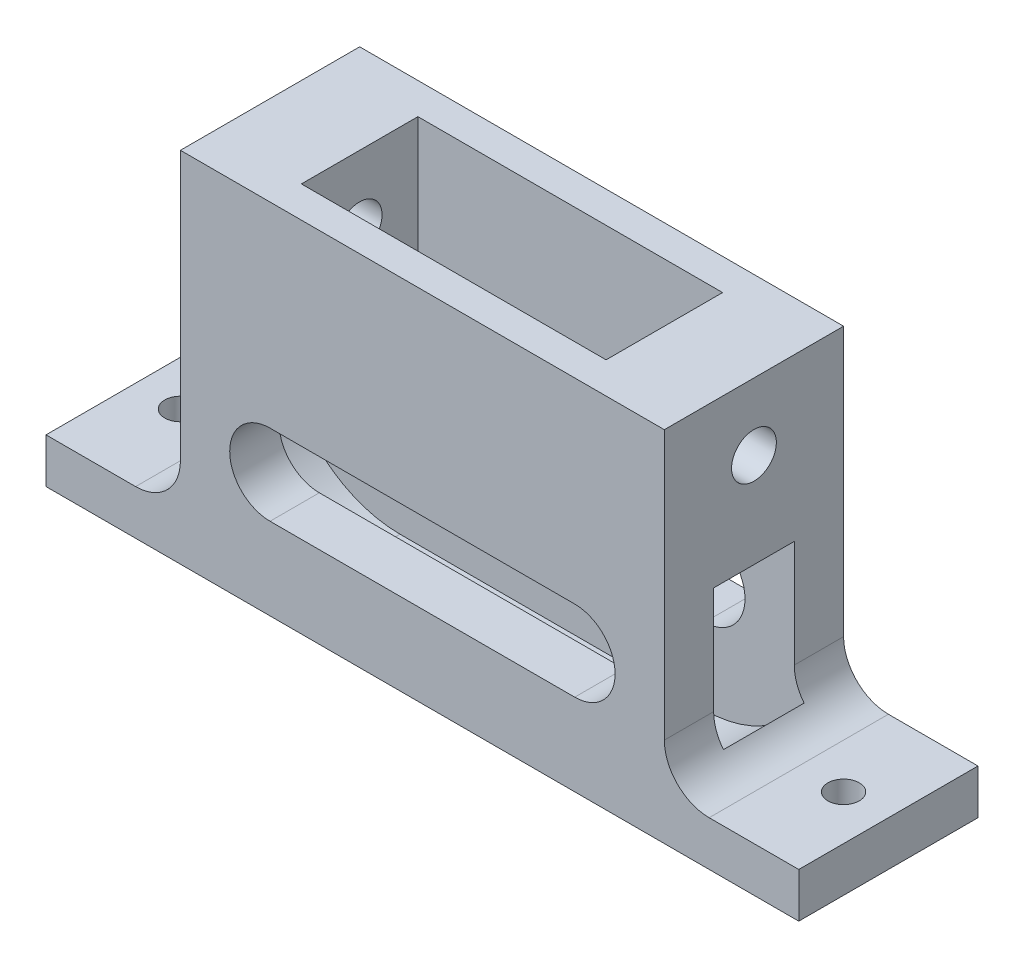
SolidWorks part; units mm, degrees
ref_plane "Front Plane" through (0, 0, 0) normal (0, 0, 1) x (1, 0, 0)
ref_plane "Top Plane" through (0, 0, 0) normal (0, 1, 0) x (1, 0, 0)
ref_plane "Right Plane" through (0, 0, 0) normal (1, 0, 0) x (0, 0, -1)
sketch "Sketch1" plane through (0, 0, 0) normal (0, 1, 0) x (1, 0, 0)
  line L1 (-27, 10) -> (27, 10)
  line L2 (-27, 10) -> (-27, -10)
  line L3 (-27, -10) -> (27, -10)
  line L4 (27, 10) -> (27, -10)
  line L5 (-27, 10) -> (27, -10) construction
  line L6 (-27, -10) -> (27, 10) construction
  point P0 (0, 0)
  dimension "D1" = 20
  dimension "D2" = 54
extrude "Boss-Extrude1" add sketch "Sketch1" along normal blind 40
sketch "Sketch4" plane through (0, 0, 0) normal (0, -1, 0) x (1, 0, 0)
  line L0 (27, -10) -> (-27, -10) construction
  line L1 (-27, 10) -> (-42, 10)
  line L2 (-27, 10) -> (-27, -10)
  line L3 (-27, -10) -> (-42, -10)
  line L4 (-42, 10) -> (-42, -10)
  line L5 (0, -55) -> (0, 55) construction
  line L6 (42, 10) -> (42, -10)
  line L7 (27, -10) -> (42, -10)
  line L8 (27, 10) -> (27, -10)
  line L9 (27, 10) -> (42, 10)
  dimension "D1" = 15
extrude "Boss-Extrude2" add sketch "Sketch4" against normal blind 5
fillet "Fillet1" radius 5 2 edges at (27, 5, 0) (-27, 5, 0)
sketch "Sketch6" plane through (0, 40, 0) normal (0, -1, 0) x (1, 0, 0)
  line L0 (17, 6.5) -> (-17, -6.5) construction
  line L1 (-17, 6.5) -> (17, 6.5)
  line L2 (-17, 6.5) -> (-17, -6.5)
  line L3 (-17, -6.5) -> (17, -6.5)
  line L4 (17, 6.5) -> (17, -6.5)
  line L5 (-27, -10) -> (-27, 10) construction
  point P4 (-22.3277, -5.1978)
  dimension "D1" = 10
  dimension "D2" = 13
extrude "Cut-Extrude3" cut sketch "Sketch6" along normal offset from surface (26.35 mm away) 13.65 up to face at (0, 0, 0)
sketch "Sketch7" plane through (0, 0, 10) normal (0, 0, 1) x (1, 0, 0)
  line L0 (-17, 13.65) -> (17, 13.65) construction
  line L4 (-17, 18.15) -> (17, 18.15)
  line L8 (-17, 9.15) -> (17, 9.15)
  line L9 (0, 0) -> (0, 40) construction
  line L10 (-27, 40) -> (27, 40) construction
  line L11 (-17, 13.65) -> (-17, 40) construction
  line L12 (-42, 0) -> (42, 0) construction
  arc A2 (-17, 18.15) -> (-17, 9.15) centre (-17, 13.65) ccw
  arc A3 (17, 9.15) -> (17, 18.15) centre (17, 13.65) ccw
  point P2 (0, 13.65)
  point P7 (0, 24.0363)
  point P12 (0, 23.0962)
  point P13 (0, 0)
  point P14 (0, 0)
  dimension "D1" = 9
  dimension "D2" = 13.65
extrude "Cut-Extrude4" cut sketch "Sketch7" against normal through all
sketch "Sketch3" plane through (-27, 0, 0) normal (-1, 0, 0) x (0, 0, 1)
  line L2 (-10, 32.52) -> (10, 32.52) construction
  line L3 (-10, 40) -> (-10, 10) construction
  line L4 (10, 40) -> (10, 10) construction
  line L6 (10, 0) -> (-10, 0) construction
  line L7 (-10, 40) -> (-10, 10) construction
  line L8 (-10, 13.65) -> (-10, 32.52) construction
  circle A0 centre (0, 32.52) radius 2.5
  point P2 (0, 0)
  dimension "D1" = 5
  dimension "D2" = 13.65
  dimension "D3" = 18.87
extrude "Cut-Extrude2" cut sketch "Sketch3" against normal through all
ref_plane "Plane2" through (0, 0, -4.5) normal (0, 0, -1) x (-1, 0, 0)
sketch "Sketch8" plane through (0, 0, -4.5) normal (0, 0, -1) x (-1, 0, 0)
  line L0 (-17, 13.65) -> (17, 13.65) construction
  line L1 (-17, 26.65) -> (17, 26.65)
  line L2 (-17, 0.65) -> (17, 0.65)
  arc A1 (-17, 26.65) -> (-17, 0.65) centre (-17, 13.65) ccw
  arc A2 (17, 0.65) -> (17, 26.65) centre (17, 13.65) ccw
  point P3 (0, 13.65)
  dimension "D1" = 13
extrude "Cut-Extrude5" cut sketch "Sketch8" against normal blind 9
sketch "Sketch9" plane through (0, 5, 0) normal (0, 1, 0) x (1, 0, 0)
  line L0 (-32, 0) -> (-42, 0) construction
  line L1 (-32, -10) -> (-32, 10) construction
  line L2 (-42, -10) -> (-42, 10) construction
  line L3 (32, 0) -> (42, 0) construction
  line L4 (32, 10) -> (32, -10) construction
  line L5 (42, 10) -> (42, -10) construction
  circle A0 centre (-37, 0) radius 1.75
  circle A1 centre (37, 0) radius 1.75
  point P10 (37, 0)
  dimension "D1" = 3.5
  dimension "D2" = 3.5
extrude "Cut-Extrude6" cut sketch "Sketch9" against normal through all
